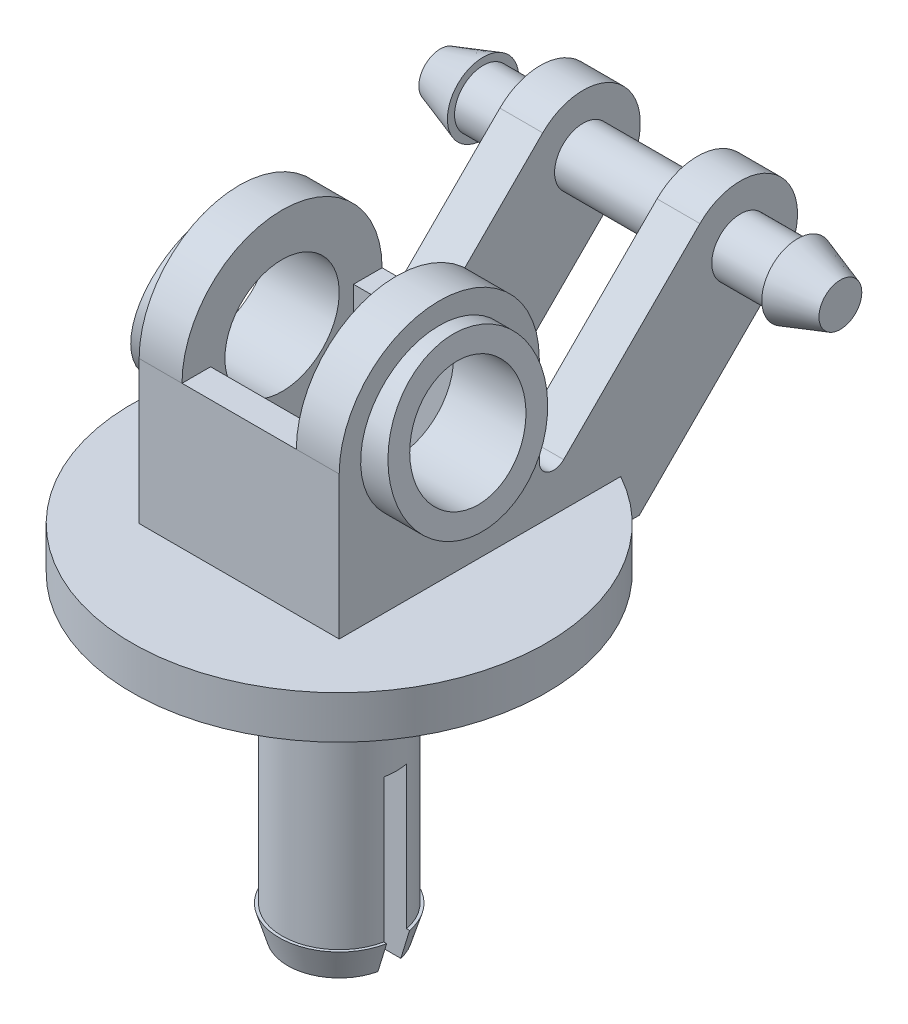
SolidWorks part; units mm, degrees
ref_plane "前视基准面" through (0, 0, 0) normal (0, 0, 1) x (1, 0, 0)
ref_plane "上视基准面" through (0, 0, 0) normal (0, 1, 0) x (1, 0, 0)
ref_plane "右视基准面" through (0, 0, 0) normal (1, 0, 0) x (0, 0, -1)
sketch "草图1" plane through (0, 0, 0) normal (0, 1, 0) x (1, 0, 0)
  circle A0 centre (0, 0) radius 7.25
  dimension "D1" = 14.5
extrude "凸台-拉伸1" add sketch "草图1" along normal blind 1.5
ref_plane "基准面1" through (3.5, 0, 0) normal (1, 0, 0) x (0, 0, -1)
sketch "草图2" plane through (3.5, 0, 0) normal (1, 0, 0) x (0, 0, -1)
  line L0 (0, 0) -> (-3.5, 0)
  line L1 (-3.5, 0) -> (-3.5, 6.5)
  line L2 (0, 0) -> (0, 6.5) construction
  line L3 (0, 0) -> (7, 0)
  line L4 (7, 0) -> (11.9497, 4.9497)
  line L5 (11.9497, 4.9497) -> (10.5355, 6.364) construction
  line L6 (3.5, 6.5) -> (3.5, 2.1569)
  line L7 (9.1213, 7.7782) -> (3.5, 2.1569)
  line L8 (10.5355, 6.364) -> (9.1213, 7.7782) construction
  arc A0 (3.5, 6.5) -> (-3.5, 6.5) centre (0, 6.5) ccw
  arc A1 (11.9497, 4.9497) -> (9.1213, 7.7782) centre (10.5355, 6.364) ccw
  dimension "D3" = 7
  dimension "D1" = 3.5
  dimension "D2" = 6.5
  dimension "D5" = 90
  dimension "D6" = 7
  dimension "D7" = 135
  dimension "D8" = 7
  dimension "D9" = 90
  dimension "D10" = 2
  dimension "D11" = 45
extrude "凸台-拉伸2" add sketch "草图2" against normal blind 1.5
fillet "圆角1" radius 0.5 1 edges at (2.75, 2.1569, -3.5)
sketch "草图3" plane through (3.5, 0, 0) normal (1, 0, 0) x (0, 0, -1)
  circle A0 centre (0, 6.5) radius 2
  dimension "D1" = 4
extrude "切除-拉伸1" cut sketch "草图3" against normal up to next
sketch "草图4" plane through (3.5, 0, 0) normal (1, 0, 0) x (0, 0, -1)
  circle A0 centre (0, 6.5) radius 2
  circle A1 centre (0, 6.5) radius 2.75
  dimension "D1" = 4
  dimension "D2" = 5.5
extrude "凸台-拉伸3" add sketch "草图4" along normal blind 1.5
sketch "草图5" plane through (0, 0, 3.5) normal (0, 0, 1) x (1, 0, 0)
  line L0 (5, 9.25) -> (4, 9.25)
  line L1 (5, 9.25) -> (3.5, 9.25) construction
  line L2 (4, 9.25) -> (5, 3.75)
  line L3 (5, 3.75) -> (5, 9.25)
  dimension "D1" = 1
extrude "切除-拉伸2" cut sketch "草图5" against normal up to next
sketch "草图6" plane through (3.5, 0, 0) normal (1, 0, 0) x (0, 0, -1)
  circle A0 centre (10.5355, 6.364) radius 1
  dimension "D1" = 2
extrude "凸台-拉伸4" add sketch "草图6" along normal blind 2
sketch "草图7" plane through (5.5, 0, 0) normal (1, 0, 0) x (0, 0, -1)
  line L0 (10.5355, 6.364) -> (9.2855, 6.364) construction
  circle A0 centre (10.5355, 6.364) radius 1.25
  dimension "D1" = 2.5
ref_plane "基准面2" through (7, 0, 0) normal (1, 0, 0) x (0, 0, -1)
sketch "草图8" plane through (7, 0, 0) normal (1, 0, 0) x (0, 0, -1)
  line L0 (10.5355, 6.364) -> (9.7855, 6.364) construction
  circle A0 centre (10.5355, 6.364) radius 0.75
  dimension "D1" = 1.5
loft "放样1" add profiles "草图7", "草图8" connector at (5.5, 6.3522, -9.2856) connector at (7, 6.3503, -9.7857)
sketch "草图9" plane through (2, 0, 0) normal (-1, 0, 0) x (0, 0, 1)
  line L0 (7.25, 1.5) -> (-7.25, 1.5) construction
  line L1 (3.5, 6.5) -> (2.5, 6.5)
  line L2 (3.5, 6.5) -> (3.5, 1.5)
  line L3 (3.5, 1.5) -> (2.5, 1.5)
  line L4 (2.5, 6.5) -> (2.5, 1.5)
  line L5 (3.5, 1.5) -> (-6.9687, 1.5) construction
  line L6 (-3.5, 6.5) -> (-2.5, 6.5)
  line L7 (-3.5, 6.5) -> (-3.5, 1.5)
  line L8 (-3.5, 1.5) -> (-2.5, 1.5)
  line L9 (-2.5, 6.5) -> (-2.5, 1.5)
  circle A0 centre (-10.5355, 6.364) radius 1
  dimension "D1" = 2
  dimension "D2" = 1
  dimension "D3" = 1
extrude "凸台-拉伸5" add sketch "草图9" along normal blind 2
mirror "镜向1" about plane through (0, 0, 0) normal (1, 0, 0) of "凸台-拉伸5", "放样1", "凸台-拉伸4", "切除-拉伸2", "凸台-拉伸3", "切除-拉伸1", "圆角1", "凸台-拉伸2"
sketch "草图10" plane through (0, 0, 0) normal (0, -1, 0) x (1, 0, 0)
  circle A0 centre (0, 0) radius 3
  dimension "D1" = 6
extrude "凸台-拉伸6" add sketch "草图10" along normal blind 1
sketch "草图11" plane through (0, -1, 0) normal (0, -1, 0) x (1, 0, 0)
  circle A0 centre (0, 0) radius 2
  dimension "D1" = 4
extrude "凸台-拉伸7" add sketch "草图11" along normal blind 9
sketch "草图12" plane through (0, -10, 0) normal (0, -1, 0) x (1, 0, 0)
  line L0 (0, 0) -> (0, 2.1) construction
  circle A0 centre (0, 0) radius 2.1
  dimension "D1" = 4.2
ref_plane "基准面3" through (0, -11, 0) normal (0, -1, 0) x (-1, 0, 0)
sketch "草图13" plane through (0, -11, 0) normal (0, -1, 0) x (-1, 0, 0)
  line L0 (0, 0) -> (0, -1.8) construction
  circle A0 centre (0, 0) radius 1.8
  dimension "D1" = 3.6
loft "放样2" add profiles "草图12", "草图13" connector at (0.0185, -10, 2.0999) connector at (-0.0057, -11, 1.8)
sketch "草图14" plane through (0, -11, 0) normal (0, -1, 0) x (1, 0, 0)
  line L0 (4, 0.4) -> (4, -0.4)
  line L1 (4, 0.4) -> (-4, 0.4)
  line L2 (4, -0.4) -> (-4, -0.4)
  line L3 (-4, 0.4) -> (-4, -0.4)
  line L4 (4, 0.4) -> (-4, -0.4) construction
  line L5 (4, -0.4) -> (-4, 0.4) construction
  point P1 (0, 0)
  dimension "D1" = 0.8
  dimension "D2" = 8
extrude "切除-拉伸3" cut sketch "草图14" against normal blind 6
